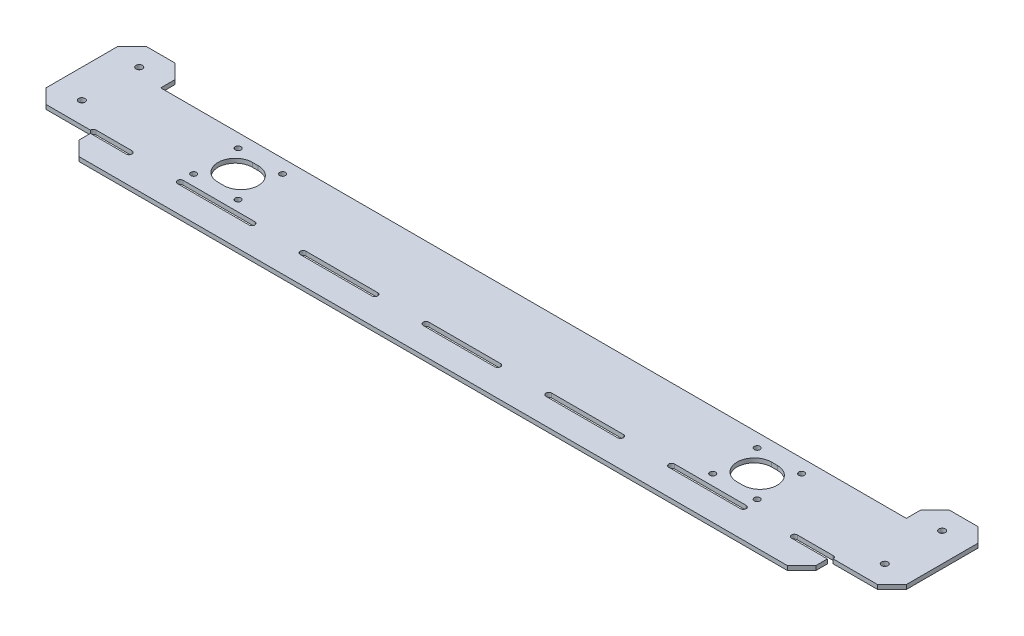
SolidWorks part; units mm, degrees
ref_plane "Front Plane" through (0, 0, 0) normal (0, 0, 1) x (1, 0, 0)
ref_plane "Top Plane" through (0, 0, 0) normal (0, 1, 0) x (1, 0, 0)
ref_plane "Right Plane" through (0, 0, 0) normal (1, 0, 0) x (0, 0, -1)
sketch "Sketch1" plane through (0, 0, 0) normal (0, 1, 0) x (1, 0, 0)
  line L0 (0, 0) -> (40, 0)
  line L1 (300, 2) -> (300, 50)
  line L2 (300, 50) -> (40, 50)
  line L3 (40, 50) -> (40, 70)
  line L4 (40, 70) -> (0, 70)
  line L5 (0, 70) -> (0, 0)
  line L6 (40, 0) -> (41, 0)
  line L7 (43, -2) -> (43, -20)
  line L8 (43, -20) -> (300, -20)
  line L9 (300, -20) -> (300, -2)
  line L10 (43, 0) -> (128.6667, 0) construction
  line L11 (128.6667, 0) -> (214.3333, 0) construction
  line L12 (214.3333, 0) -> (300, 0) construction
  line L13 (103.6667, 0) -> (153.6667, 0) construction
  line L14 (103.6667, 2) -> (153.6667, 2)
  line L15 (103.6667, -2) -> (153.6667, -2)
  line L16 (189.3333, 0) -> (239.3333, 0) construction
  line L17 (189.3333, 2) -> (239.3333, 2)
  line L18 (189.3333, -2) -> (239.3333, -2)
  line L19 (68, 0) -> (43, 0) construction
  line L20 (68, -2) -> (43, -2)
  line L21 (68, 2) -> (43, 2)
  line L22 (275, 0) -> (300, 0) construction
  line L23 (275, 2) -> (300, 2)
  line L24 (275, -2) -> (300, -2)
  arc A0 (103.6667, 2) -> (103.6667, -2) centre (103.6667, 0) ccw
  arc A1 (153.6667, -2) -> (153.6667, 2) centre (153.6667, 0) ccw
  arc A2 (189.3333, 2) -> (189.3333, -2) centre (189.3333, 0) ccw
  arc A3 (239.3333, -2) -> (239.3333, 2) centre (239.3333, 0) ccw
  arc A4 (68, -2) -> (68, 2) centre (68, 0) ccw
  arc A5 (43, 2) -> (41, 0) centre (43, 0) ccw
  arc A6 (275, 2) -> (275, -2) centre (275, 0) ccw
  point P15 (128.6667, 0)
  point P21 (214.3333, 0)
  point P28 (55.5, 0)
  point P34 (287.5, 0)
  point P39 (305.5928, 62.3115)
  dimension "D10" = 2
  dimension "D1" = 40
  dimension "D2" = 3
  dimension "D3" = 20
  dimension "D4" = 50
  dimension "D5" = 20
  dimension "D6" = 300
  dimension "D7" = 257
  dimension "D8" = 50
  dimension "D9" = 50
  dimension "D11" = 25
  dimension "D12" = 25
extrude "Boss-Extrude1" add sketch "Sketch1" along normal blind 3
chamfer "Chamfer1" distance 10 angle 45 4 edges at (40, 1.5, -70) (0, 1.5, -70) (0, 1.5, 0) (43, 1.5, 20)
sketch "Sketch2" plane through (0, 3, 0) normal (0, 1, 0) x (1, 0, 0)
  line L0 (20, 70) -> (20, 0) construction
  line L1 (30, 70) -> (10, 70) construction
  line L2 (10, 0) -> (41, 0) construction
  circle A0 centre (20, 55) radius 2.25
  circle A1 centre (20, 15) radius 2.25
  dimension "D1" = 4.5
  dimension "D2" = 15
  dimension "D3" = 15
extrude "Cut-Extrude1" cut sketch "Sketch2" against normal blind 3
sketch "Sketch3" plane through (0, 3, 0) normal (0, 1, 0) x (1, 0, 0)
  line L0 (40, 50) -> (40, 0) construction
  line L1 (10, 0) -> (41, 0) construction
  line L2 (40, 25) -> (300, 25) construction
  line L3 (300, -20) -> (300, -2) construction
  line L4 (117, 25) -> (121, 25) construction
  line L5 (117, 37) -> (121, 37)
  line L6 (117, 13) -> (121, 13)
  line L7 (119, 25) -> (99.0568, 44.9432) construction
  line L8 (119, 25) -> (138.4592, 5.5408) construction
  line L9 (119, 25) -> (100.845, 6.845) construction
  line L10 (119, 25) -> (134.1665, 40.1665) construction
  line L11 (103.5, 40.5) -> (134.5, 40.5) construction
  line L12 (134.5, 40.5) -> (134.5, 9.5) construction
  line L13 (134.5, 9.5) -> (103.5, 9.5) construction
  line L14 (103.5, 9.5) -> (103.5, 40.5) construction
  arc A0 (117, 37) -> (117, 13) centre (117, 25) ccw
  arc A1 (121, 13) -> (121, 37) centre (121, 25) ccw
  circle A2 centre (103.5, 40.5) radius 2
  circle A3 centre (134.5, 40.5) radius 2
  circle A4 centre (134.5, 9.5) radius 2
  circle A5 centre (103.5, 9.5) radius 2
  point P11 (119, 25)
  dimension "D3" = 12
  dimension "D4" = 4
  dimension "D1" = 79
  dimension "D2" = 4
  dimension "D5" = 31
extrude "Cut-Extrude2" cut sketch "Sketch3" against normal blind 3
ref_plane "Plane1" through (300, 0, 0) normal (1, 0, 0) x (0, 0, -1)
mirror "Mirror3" about plane through (300, 0, 0) normal (1, 0, 0) of bodies 103
